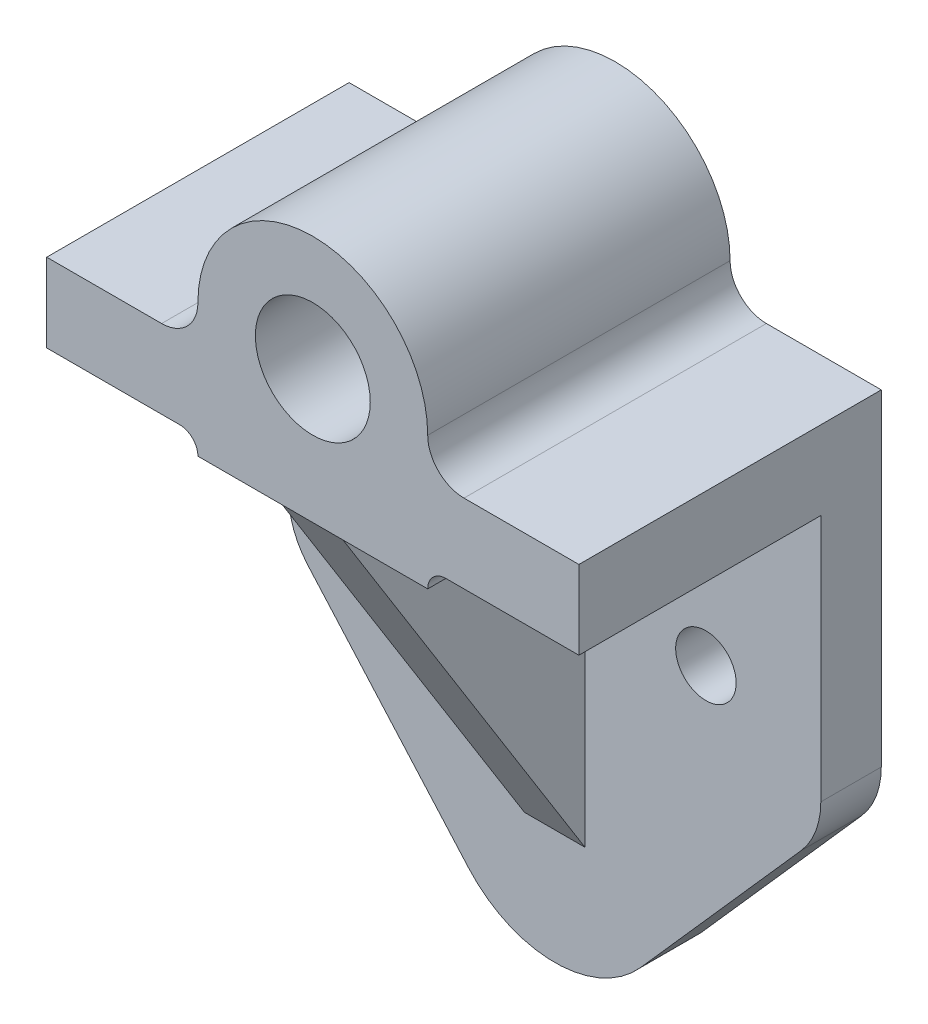
SolidWorks part; units mm, degrees
ref_plane "Front Plane" through (0, 0, 0) normal (0, 0, 1) x (1, 0, 0)
ref_plane "Top Plane" through (0, 0, 0) normal (0, 1, 0) x (1, 0, 0)
ref_plane "Right Plane" through (0, 0, 0) normal (1, 0, 0) x (0, 0, -1)
sketch "Sketch1" plane through (0, 0, 0) normal (0, 0, 1) x (1, 0, 0)
  line L0 (-44, -6) -> (-25, -6)
  line L1 (44, -6) -> (44, -60)
  line L2 (40.7387, -68.6115) -> (14.2335, -98.586)
  line L3 (-14.2335, -98.586) -> (-40.7387, -68.6115)
  line L4 (-44, -60) -> (-44, -6)
  line L5 (25, -6) -> (44, -6)
  line L6 (-44, -19) -> (-19, -19)
  line L7 (-19, -19) -> (-19, -22)
  line L8 (-19, -22) -> (19, -22)
  line L9 (19, -22) -> (19, -19)
  line L10 (19, -19) -> (44, -19)
  circle A0 centre (0, 0) radius 9.5
  arc A1 (19, 0) -> (-19, 0) centre (0, 0) ccw
  arc A2 (44, -60) -> (40.7387, -68.6115) centre (31, -60) cw
  arc A3 (14.2335, -98.586) -> (-14.2335, -98.586) centre (0, -86) cw
  arc A4 (-40.7387, -68.6115) -> (-44, -60) centre (-31, -60) cw
  circle A5 centre (-25, -50) radius 5
  circle A6 centre (25, -50) radius 5
  arc A7 (-19, 0) -> (-25, -6) centre (-25, 0) cw
  arc A8 (19, 0) -> (25, -6) centre (25, 0) ccw
  point P21 (0, -22)
  point P31 (18.0278, -6)
  dimension "D1" = 19
  dimension "D2" = 13
  dimension "D8" = 19
  dimension "D9" = 19
  dimension "D13" = 10
  dimension "D17" = 6
  dimension "D18" = 6
  dimension "D3" = 38
  dimension "D4" = 13
  dimension "D5" = 88
  dimension "D6" = 3
  dimension "D7" = 22
  dimension "D10" = 44
  dimension "D11" = 105
  dimension "D12" = 45
  dimension "D14" = 19
  dimension "D15" = 50
  dimension "D16" = 19
extrude "Boss-Extrude1" add sketch "Sketch1" along normal blind 10 contours A4 L3 A3 L2 A2 L1 L10 L9 L8 L7 L6 L4 A6 A5 region at (0, -55.7935, 0)
extrude "Boss-Extrude2" add sketch "Sketch1<3>" along normal blind 50 contours A8 A1 A7 L0 L4 L6 L7 L8 L9 L10 L1 L5 A0 region at (-34.5, -6.9708, 0)
sketch "Sketch1<3>" plane through (0, 0, 0) normal (0, 0, 1) x (1, 0, 0) same geometry as "Sketch1"
sketch "Sketch2" plane through (0, 0, 0) normal (1, 0, 0) x (0, 0, -1)
  line L0 (-50, -22) -> (-10, -86)
  line L1 (-10, -68.6115) -> (-10, -98.586) construction
  line L2 (-10, -105) -> (0, -105) construction
  dimension "D1" = 19
rib "Rib1" sketch "Sketch2" sketch "Sketch2" thickness 10 extrusion direction parallel to sketch draft on no parameters "D1"=10
fillet "Fillet1" radius 3 2 edges at (-19, -19, 30) (19, -19, 30)
equation "\"D10@Sketch1\"=\"D5@Sketch1\"/2"
equation "\"D16@Sketch1\"=\"D14@Sketch1\""
